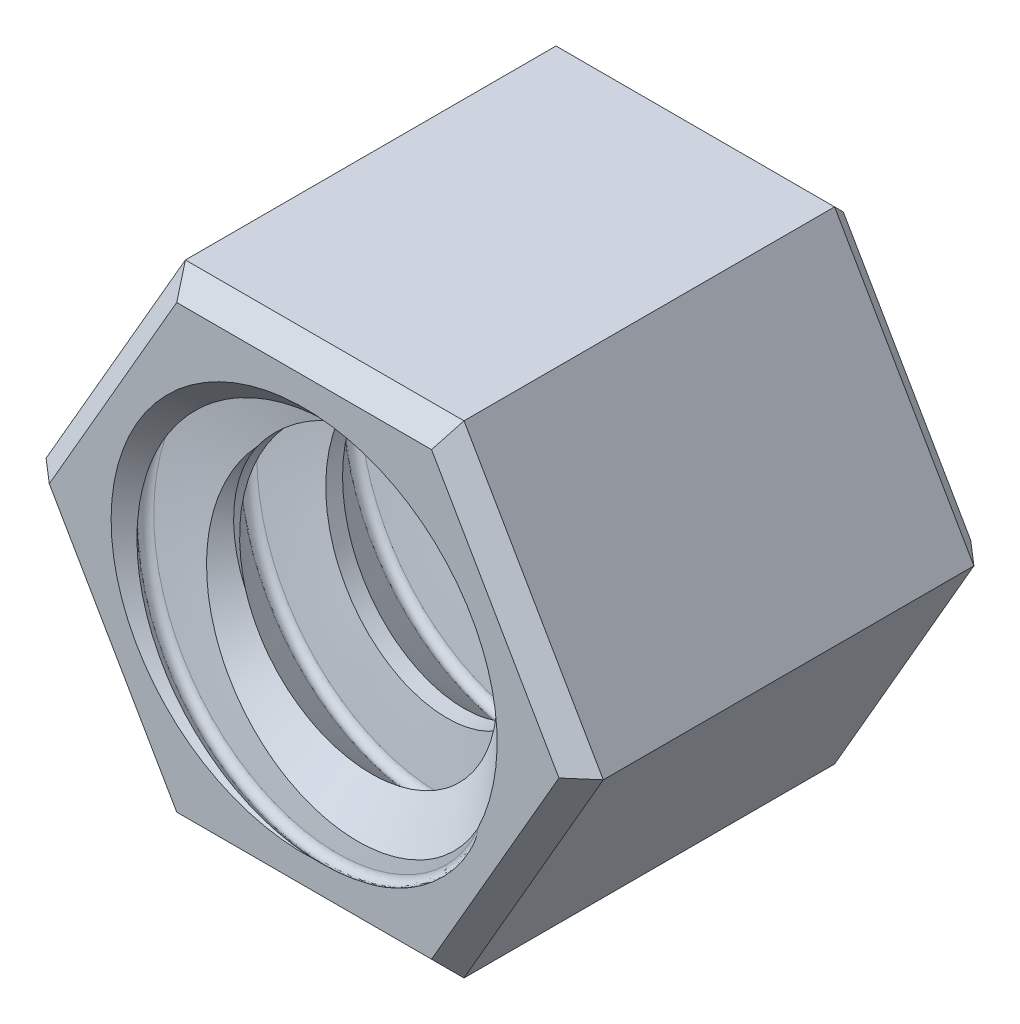
SolidWorks part; units mm, degrees
material "ABS"
ref_plane "Front Plane" through (0, 0, 0) normal (0, 0, 1) x (1, 0, 0)
ref_plane "Top Plane" through (0, 0, 0) normal (0, 1, 0) x (1, 0, 0)
ref_plane "Right Plane" through (0, 0, 0) normal (1, 0, 0) x (0, 0, -1)
sketch "Sketch2" plane through (0, 0, 0) normal (1, 0, 0) x (0, 0, -1)
  line L1 (-10.16, -12.7) -> (10.16, -12.7)
  line L2 (-10.16, -12.7) -> (-10.16, 12.7)
  line L3 (-10.16, 12.7) -> (10.16, 12.7)
  line L4 (10.16, -12.7) -> (10.16, 12.7)
  line L5 (-10.16, -12.7) -> (10.16, 12.7) construction
  line L6 (-10.16, 12.7) -> (10.16, -12.7) construction
  point P0 (0, 0)
  dimension "D1" = 20.32
  dimension "D2" = 25.4
extrude "Boss-Extrude1" add sketch "Sketch2" along normal mid plane 31.75
sketch "Sketch6" plane through (0, 0, 0) normal (0, 0, 1) x (1, 0, 0)
  line L1 (13.7482, 0) -> (6.8741, 11.9063)
  line L2 (6.8741, 11.9063) -> (-6.8741, 11.9063)
  line L3 (-6.8741, 11.9063) -> (-13.7482, 0)
  line L4 (-13.7482, 0) -> (-6.8741, -11.9062)
  line L5 (-6.8741, -11.9062) -> (6.8741, -11.9062)
  line L6 (6.8741, -11.9062) -> (13.7482, 0)
  circle A0 centre (0, 0) radius 11.9062 construction
  dimension "D1" = 23.8125
sketch "Sketch3" plane through (0, 0, 10.16) normal (0, 0, 1) x (1, 0, 0)
  circle A0 centre (0, 0) radius 6.5024
  dimension "D1" = 13.0048
extrude "Cut-Extrude1" cut sketch "Sketch3" against normal through all
ref_plane "ThreadStart" through (0, 0, -15.24) normal (0, 0, -1) x (-1, 0, 0)
sketch "Sketch4" plane through (0, 0, -15.24) normal (0, 0, 1) x (1, 0, 0)
  circle A0 centre (0, 0) radius 6.5024
  circle A1 centre (0, 0) radius 6.5024 construction
curve "Helix/Spiral1" pitch 5.08 height 35.56 radius 6.5024 centre (0, 0, -15.24) axis (0, 0, 1) start towards (1, 0, 0)
sketch "Sketch5" plane through (0, 0, 0) normal (0, 1, 0) x (1, 0, 0)
  line L0 (6.5024, 15.24) -> (9.5504, 14.8658)
  line L1 (11.176, 15.24) -> (-11.176, 15.24) construction
  line L2 (9.7627, 14.2493) -> (6.5024, 10.989)
  line L3 (6.5024, 10.989) -> (6.5024, 15.24)
  arc A0 (9.7627, 14.2493) -> (9.5504, 14.8658) centre (9.5062, 14.5057) ccw
  spline S0 degree 3 poles (6.5024, 15.24) (6.5024, 15.1348) (6.1638, 14.9222) (4.7176, 14.6051) (2.5531, 14.2875) (0, 13.97) (-2.5531, 13.6525) (-4.7176, 13.335) (-6.1638, 13.0175) (-6.6717, 12.7) (-6.1638, 12.3825) (-4.7176, 12.065) (-2.5531, 11.7475) (0, 11.43) (2.5531, 11.1125) (4.7176, 10.795) (6.1638, 10.4775) (6.6717, 10.16) (6.1638, 9.8425) (4.7176, 9.525) (2.5531, 9.2075) (0, 8.89) (-2.5531, 8.5725) (-4.7176, 8.255) (-6.1638, 7.9375) (-6.6717, 7.62) (-6.1638, 7.3025) (-4.7176, 6.985) (-2.5531, 6.6675) (0, 6.35) (2.5531, 6.0325) (4.7176, 5.715) (6.1638, 5.3975) (6.6717, 5.08) (6.1638, 4.7625) (4.7176, 4.445) (2.5531, 4.1275) (0, 3.81) (-2.5531, 3.4925) (-4.7176, 3.175) (-6.1638, 2.8575) (-6.6717, 2.54) (-6.1638, 2.2225) (-4.7176, 1.905) (-2.5531, 1.5875) (0, 1.27) (2.5531, 0.9525) (4.7176, 0.635) (6.1638, 0.3175) (6.6717, 0) (6.1638, -0.3175) (4.7176, -0.635) (2.5531, -0.9525) (0, -1.27) (-2.5531, -1.5875) (-4.7176, -1.905) (-6.1638, -2.2225) (-6.6717, -2.54) (-6.1638, -2.8575) (-4.7176, -3.175) (-2.5531, -3.4925) (0, -3.81) (2.5531, -4.1275) (4.7176, -4.445) (6.1638, -4.7625) (6.6717, -5.08) (6.1638, -5.3975) (4.7176, -5.715) (2.5531, -6.0325) (0, -6.35) (-2.5531, -6.6675) (-4.7176, -6.985) (-6.1638, -7.3025) (-6.6717, -7.62) (-6.1638, -7.9375) (-4.7176, -8.255) (-2.5531, -8.5725) (0, -8.89) (2.5531, -9.2075) (4.7176, -9.525) (6.1638, -9.8425) (6.6717, -10.16) (6.1638, -10.4775) (4.7176, -10.795) (2.5531, -11.1125) (0, -11.43) (-2.5531, -11.7475) (-4.7176, -12.065) (-6.1638, -12.3825) (-6.6717, -12.7) (-6.1638, -13.0175) (-4.7176, -13.335) (-2.5531, -13.6525) (0, -13.97) (2.5531, -14.2875) (4.7176, -14.605) (6.1638, -14.9225) (6.6717, -15.24) (6.1638, -15.5575) (4.7176, -15.875) (2.5531, -16.1925) (0, -16.51) (-2.5531, -16.8275) (-4.7176, -17.145) (-6.1638, -17.4625) (-6.6717, -17.78) (-6.1638, -18.0975) (-4.7176, -18.415) (-2.5531, -18.7325) (0, -19.05) (2.5531, -19.3675) (4.7176, -19.6851) (6.1638, -20.0022) (6.5024, -20.2148) (6.5024, -20.32) knots 0 0 0 0 0.008929 0.017857 0.026786 0.035714 0.044643 0.053571 0.0625 0.071429 0.080357 0.089286 0.098214 0.107143 0.116071 0.125 0.133929 0.142857 0.151786 0.160714 0.169643 0.178571 0.1875 0.196429 0.205357 0.214286 0.223214 0.232143 0.241071 0.25 0.258929 0.267857 0.276786 0.285714 0.294643 0.303571 0.3125 0.321429 0.330357 0.339286 0.348214 0.357143 0.366071 0.375 0.383929 0.392857 0.401786 0.410714 0.419643 0.428571 0.4375 0.446429 0.455357 0.464286 0.473214 0.482143 0.491071 0.5 0.508929 0.517857 0.526786 0.535714 0.544643 0.553571 0.5625 0.571429 0.580357 0.589286 0.598214 0.607143 0.616071 0.625 0.633929 0.642857 0.651786 0.660714 0.669643 0.678571 0.6875 0.696429 0.705357 0.714286 0.723214 0.732143 0.741071 0.75 0.758929 0.767857 0.776786 0.785714 0.794643 0.803571 0.8125 0.821429 0.830357 0.839286 0.848214 0.857143 0.866071 0.875 0.883929 0.892857 0.901786 0.910714 0.919643 0.928571 0.9375 0.946429 0.955357 0.964286 0.973214 0.982143 0.991071 1 1 1 1 construction
  point P9 (10.2885, 14.7751)
  dimension "D4" = 0.3627
  dimension "D1" = 7
  dimension "D2" = 45
  dimension "D3" = 3.7861
sweep "Cut-Sweep1" cut profiles "Sketch5" path "Helix/Spiral1"
extrude "Cut-Extrude2" cut sketch "Sketch6" against normal mid plane 50.8 flip side to cut
sketch "Sketch7" plane through (0, 0, 0) normal (0, 1, 0) x (1, 0, 0)
  line L0 (0, -1000) -> (0, 49000) construction
  line L1 (0, -10.16) -> (9.525, -10.16)
  line L4 (9.525, -10.16) -> (0, -0.635)
  line L5 (0, -0.635) -> (0, -10.16)
  line L6 (0, 10.16) -> (0, 0.635)
  line L8 (0, 0.635) -> (9.525, 10.16)
  line L9 (13.7482, 10.16) -> (6.8741, 10.16) construction
  line L10 (9.525, 10.16) -> (0, 10.16)
  line L11 (-6.8741, -10.16) -> (6.8741, -10.16) construction
  dimension "D1" = 45
  dimension "D2" = 9.525
revolve "Cut-Revolve1" cut sketch "Sketch7" angle 360 about L0
chamfer "Chamfer1" distance 1.016 angle 45 12 edges at (-10.3111, 5.9531, 10.16) (-10.3111, -5.9531, 10.16) (0, -11.9062, 10.16) (10.3111, -5.9531, 10.16) (10.3111, 5.9531, 10.16) (0, 11.9063, 10.16) (-10.3111, 5.9531, -10.16) (-10.3111, -5.9531, -10.16) (0, -11.9062, -10.16) (10.3111, -5.9531, -10.16) (10.3111, 5.9531, -10.16) (0, 11.9063, -10.16)
fillet "Fillet1" [suppressed] radius 0.762
equation "\"Pitch\"= 1 / 5"
equation "\"D3@Sketch5\"=\"Pitch\"*(.8906-.1453)"
equation "\"D4@Sketch5\"=\"Pitch\"*.0714"
